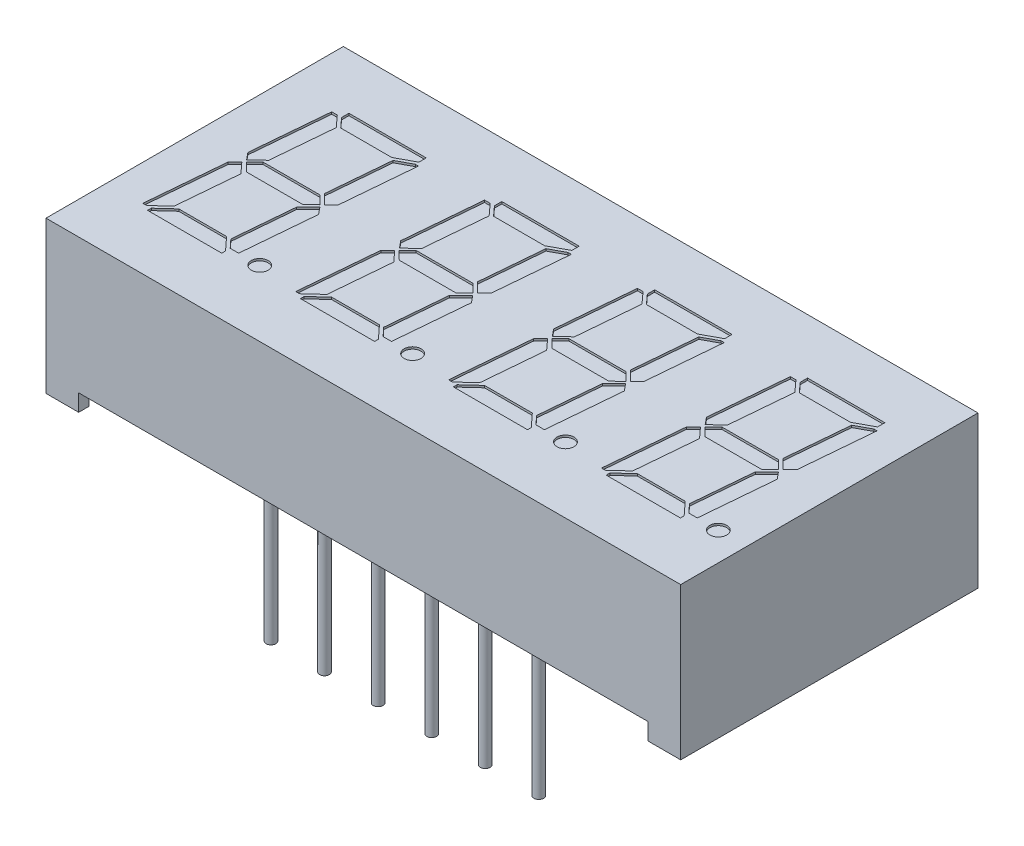
SolidWorks part; units mm, degrees
material "ABS"
ref_plane "Front Plane" through (0, 0, 0) normal (0, 0, 1) x (1, 0, 0)
ref_plane "Top Plane" through (0, 0, 0) normal (0, 1, 0) x (1, 0, 0)
ref_plane "Right Plane" through (0, 0, 0) normal (1, 0, 0) x (0, 0, -1)
sketch "Sketch1" plane through (0, 0, 0) normal (0, 1, 0) x (1, 0, 0)
  line L0 (-15.05, 0) -> (15.05, 0) construction
  line L1 (-15.05, 7.05) -> (15.05, 7.05)
  line L2 (-15.05, 7.05) -> (-15.05, -7.05)
  line L3 (-15.05, -7.05) -> (15.05, -7.05)
  line L4 (15.05, 7.05) -> (15.05, -7.05)
  point P6 (-16.1973, 7.05)
  dimension "D1" = 14.1
  dimension "D2" = 30.1
extrude "Boss-Extrude1" add sketch "Sketch1" against normal blind 7.2
sketch "Sketch2" plane through (0, 0, 7.05) normal (0, 0, 1) x (1, 0, 0)
  line L0 (0, 0) -> (0, -6.4) construction
  line L1 (-15.05, 0) -> (15.05, 0) construction
  line L2 (-15.05, -7.2) -> (15.05, -7.2) construction
  line L3 (-13.5, -6.4) -> (13.5, -6.4)
  line L4 (-13.5, -6.4) -> (-13.5, -7.2)
  line L5 (-13.5, -7.2) -> (13.5, -7.2)
  line L6 (13.5, -6.4) -> (13.5, -7.2)
  line L7 (0, -6.4) -> (0, -7.2) construction
  dimension "D1" = 27
  dimension "D2" = 6.4
extrude "Cut-Extrude1" cut sketch "Sketch2" against normal up to surface (14.1 mm away) up to face at (0, -3.6, -7.05)
sketch "Sketch3" plane through (0, -6.4, 0) normal (0, -1, 0) x (1, 0, 0)
  line L0 (13.5, 7.05) -> (-13.5, 7.05) construction
  line L1 (-14.55, 6.55) -> (14.55, 6.55)
  line L2 (-14.55, 6.55) -> (-14.55, -6.55)
  line L3 (-14.55, -6.55) -> (14.55, -6.55)
  line L4 (14.55, 6.55) -> (14.55, -6.55)
  line L5 (-14.55, 6.55) -> (14.55, -6.55) construction
  line L6 (-14.55, -6.55) -> (14.55, 6.55) construction
  line L7 (-15.05, -7.05) -> (-15.05, 7.05) construction
  point P0 (0, 0)
  dimension "D1" = 0.5
  dimension "D2" = 0.5
extrude "Cut-Extrude2" cut sketch "Sketch3" against normal blind 0.5 and the other way up to surface (0.8 mm away) other way up to face at (-14.275, -7.2, 0)
fillet "Fillet1" radius 1 4 edges at (14.55, -5.9, 0) (0, -5.9, 6.55) (-14.55, -5.9, 0) (0, -5.9, -6.55)
fillet "Fillet2" radius 0.1 8 edges at (14.55, -7.05, -6.55) (14.55, -7.05, 6.55) (-14.55, -7.05, 6.55) (-14.55, -7.05, -6.55) (14.2571, -6.1929, -6.2571) (14.2571, -6.1929, 6.2571) (-14.2571, -6.1929, 6.2571) (-14.2571, -6.1929, -6.2571)
sketch "Sketch4" plane through (0, -5.9, 0) normal (0, -1, 0) x (1, 0, 0)
  line L0 (0, 5.08) -> (0, -5.08) construction
  line L1 (-1.27, 5.08) -> (1.27, 5.08) construction
  line L2 (-1.27, -5.08) -> (1.27, -5.08) construction
  line L3 (1.27, -5.08) -> (3.81, -5.08) construction
  line L4 (3.81, -5.08) -> (6.35, -5.08) construction
  line L5 (-1.27, -5.08) -> (-3.81, -5.08) construction
  line L6 (-3.81, -5.08) -> (-6.35, -5.08) construction
  line L7 (1.27, 5.08) -> (3.81, 5.08) construction
  line L8 (3.81, 5.08) -> (6.35, 5.08) construction
  line L9 (-1.27, 5.08) -> (-3.81, 5.08) construction
  line L10 (-3.81, 5.08) -> (-6.35, 5.08) construction
  circle A0 centre (1.27, 5.08) radius 0.23
  circle A1 centre (3.81, 5.08) radius 0.23
  circle A2 centre (6.35, 5.08) radius 0.23
  circle A3 centre (-1.27, 5.08) radius 0.23
  circle A4 centre (-3.81, 5.08) radius 0.23
  circle A5 centre (-6.35, 5.08) radius 0.23
  circle A6 centre (1.27, -5.08) radius 0.23
  circle A7 centre (-1.27, -5.08) radius 0.23
  circle A8 centre (3.81, -5.08) radius 0.23
  circle A9 centre (6.35, -5.08) radius 0.23
  circle A10 centre (-3.81, -5.08) radius 0.23
  circle A11 centre (-6.35, -5.08) radius 0.23
  dimension "D3" = 0.46
  dimension "D1" = 2.54
  dimension "D2" = 10.16
extrude "Boss-Extrude2" add sketch "Sketch4" along normal offset from surface (8.1 mm away) 14 up to face at (0, 0, 0)
sketch "Sketch5" plane through (0, 0, 0) normal (0, 1, 0) x (1, 0, 0)
  line L0 (15.05, 0) -> (13.05, 0) construction
  line L1 (15.05, -7.05) -> (15.05, 7.05) construction
  line L2 (13.088, 0.4347) -> (13.012, -0.4347) construction
  line L3 (13.012, -0.4347) -> (12.7069, -3.9213)
  line L4 (13.088, 0.4347) -> (13.3931, 3.9213)
  line L5 (13.05, 0) -> (12.75, 0) construction
  line L6 (12.75, 0) -> (12.65, 0) construction
  line L7 (12.65, 0) -> (12.2469, 0) construction
  line L8 (12.2469, 0) -> (9.5531, 0) construction
  line L9 (9.5531, 0) -> (9.15, 0) construction
  line L10 (12.2469, 0.4) -> (12.2469, -0.4) construction
  line L11 (9.5531, 0.4) -> (9.5531, -0.4) construction
  line L12 (12.2469, 0.4) -> (9.5531, 0.4)
  line L13 (12.2469, -0.4) -> (9.5531, -0.4)
  line L14 (9.5531, -0.4) -> (9.15, 0)
  line L15 (9.15, 0) -> (9.5531, 0.4)
  line L16 (12.2469, 0.4) -> (12.65, 0)
  line L17 (12.65, 0) -> (12.2469, -0.4)
  line L18 (12.759, 0.1031) -> (12.741, -0.1031) construction
  line L19 (13.088, 0.4347) -> (12.759, 0.1031)
  line L20 (12.741, -0.1031) -> (13.012, -0.4347)
  line L21 (12.2962, 0.5625) -> (12.1901, -0.6498) construction
  line L22 (12.2962, 0.5625) -> (12.759, 0.1031)
  line L23 (12.2962, 0.5625) -> (12.5576, 3.5511)
  line L24 (9.6061, 0.6062) -> (9.5, -0.6062) construction
  line L25 (12.1901, -0.6498) -> (11.9389, -3.5213)
  line L26 (12.741, -0.1031) -> (12.1901, -0.6498)
  line L27 (9.15, 0) -> (9.05, 0) construction
  line L28 (9.05, 0) -> (8.75, 0) construction
  line L29 (8.788, 0.4347) -> (8.712, -0.4347) construction
  line L30 (9.059, 0.1031) -> (9.041, -0.1031) construction
  line L31 (8.788, 0.4347) -> (9.059, 0.1031)
  line L32 (9.059, 0.1031) -> (9.6061, 0.6062)
  line L33 (8.712, -0.4347) -> (9.041, -0.1031)
  line L34 (9.041, -0.1031) -> (9.5, -0.6062)
  line L35 (9.6061, 0.6062) -> (9.8637, 3.5511)
  line L38 (9.5, -0.6062) -> (9.245, -3.5213)
  line L42 (12.5576, 3.5511) -> (13.2431, 3.9213)
  line L43 (13.2431, 3.9213) -> (13.3931, 3.9213)
  line L44 (13.2431, 4.0918) -> (13.2431, 3.9213) construction
  line L45 (12.7069, -3.9213) -> (12.3069, -3.9213)
  line L46 (12.3069, -3.9213) -> (11.9389, -3.5213)
  line L47 (13.2431, 4.0918) -> (12.4076, 3.6405)
  line L48 (12.9003, 3.7362) -> (12.8291, 3.8682) construction
  line L49 (12.8647, 3.8022) -> (12.5655, 3.6405) construction
  line L50 (12.5576, 3.5511) -> (12.5655, 3.6405) construction
  line L51 (12.4076, 3.6405) -> (9.9851, 3.6405)
  line L52 (12.5655, 3.6405) -> (12.4076, 3.6405) construction
  line L53 (13.2431, 4.0918) -> (13.2431, 4.4405)
  line L54 (13.2431, 4.4405) -> (9.5753, 4.4405)
  line L55 (11.1964, 3.6405) -> (11.1964, 4.4405) construction
  line L56 (12.7069, -3.9213) -> (13.7069, -3.9213) construction
  line L57 (13.7069, -4.3213) -> (13.7069, -3.5213) construction
  line L58 (9.5753, 4.4405) -> (9.5753, 4.0918)
  line L59 (9.5753, 4.0918) -> (9.9851, 3.6405)
  line L60 (12.5576, 3.5511) -> (9.8637, 3.5511) construction
  line L61 (9.9851, 3.6405) -> (9.8716, 3.6405) construction
  line L62 (9.8637, 3.5511) -> (9.8716, 3.6405) construction
  line L63 (9.8637, 3.5511) -> (9.3727, 4.0918)
  line L64 (9.7802, 3.8662) -> (9.6692, 3.7653) construction
  line L65 (8.788, 0.4347) -> (9.108, 4.0918)
  line L66 (13.2431, 4.0918) -> (9.5753, 4.0918) construction
  line L67 (9.108, 4.0918) -> (9.3727, 4.0918)
  line L68 (9.3727, 4.0918) -> (9.5753, 4.0918) construction
  line L69 (11.735, -3.5213) -> (12.3069, -4.1429)
  line L70 (12.3069, -4.1429) -> (12.3069, -4.3213)
  line L71 (12.3069, -4.3213) -> (13.7069, -4.3213) construction
  line L72 (12.1229, -3.7213) -> (12.0125, -3.8229) construction
  line L73 (12.3069, -4.3213) -> (8.7882, -4.3213)
  line L74 (11.735, -3.5213) -> (9.4671, -3.5213)
  line L75 (11.9389, -3.5213) -> (11.735, -3.5213) construction
  line L76 (12.3069, -4.1429) -> (12.3069, -3.9213) construction
  line L77 (8.712, -0.4347) -> (8.3875, -4.1429)
  line L78 (8.3875, -4.1429) -> (8.566, -4.1429)
  line L79 (8.566, -4.1429) -> (9.245, -3.5213)
  line L80 (9.4671, -3.5213) -> (9.245, -3.5213) construction
  line L81 (9.4671, -3.5213) -> (8.7882, -4.1429)
  line L82 (8.7882, -4.1429) -> (8.7882, -4.3213)
  line L83 (8.9055, -3.8321) -> (9.0068, -3.9427) construction
  line L84 (8.566, -4.1429) -> (8.7882, -4.1429) construction
  circle A0 centre (13.7069, -3.9213) radius 0.4
  point P56 (9.25, -4.1481)
  point P70 (9.2888, -4.1429)
  dimension "D11" = 0.15
  dimension "D14" = 0.8
  dimension "D1" = 0.15
  dimension "D2" = 3.5
  dimension "D3" = 3.5
  dimension "D4" = 85
  dimension "D5" = 0.8
  dimension "D6" = 2
  dimension "D7" = 0.8
  dimension "D8" = 0.3
  dimension "D9" = 0.1
  dimension "D10" = 3
  dimension "D12" = 0.8
  dimension "D13" = 0.15
  dimension "D15" = 1
  dimension "D16" = 3.6678
  dimension "D17" = 0.4
  dimension "D18" = 0.15
  dimension "D19" = 0.8
  dimension "D20" = 0.15
extrude "Cut-Extrude3" cut sketch "Sketch5" against normal blind 0.1
pattern_linear "LPattern1" count 4 spacing 7.25 along (1, 0, 0) of "Cut-Extrude3"
